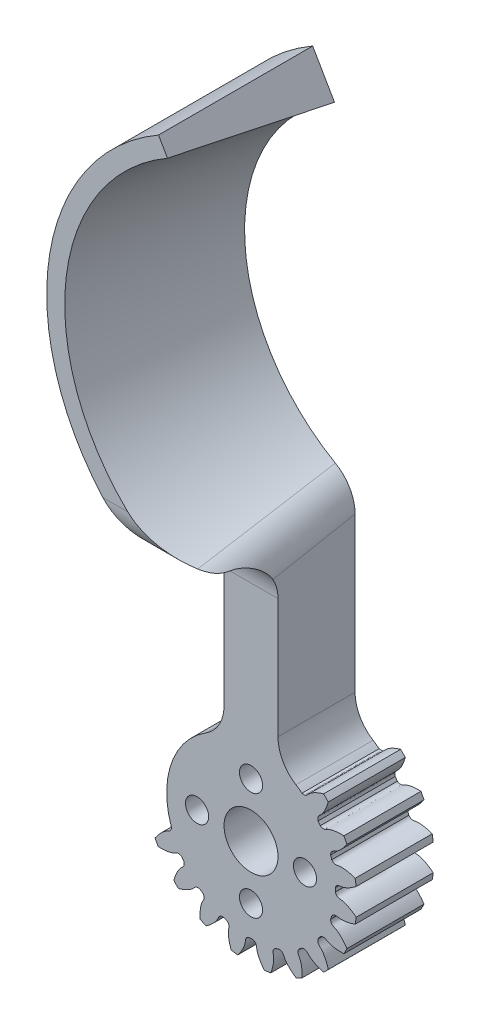
SolidWorks part; units mm, degrees
material "聚脂树脂"
ref_plane "前视基准面" through (0, 0, 0) normal (0, 0, 1) x (1, 0, 0)
ref_plane "上视基准面" through (0, 0, 0) normal (0, 1, 0) x (1, 0, 0)
ref_plane "右视基准面" through (0, 0, 0) normal (1, 0, 0) x (0, 0, -1)
other "Configuration Table"
sketch "草图1" plane through (0, 0, 0) normal (0, 0, 1) x (1, 0, 0)
  circle A0 centre (0, 0) radius 13.75
extrude "凸台-拉伸1" add sketch "草图1" along normal blind 10
ref_axis "基准轴1" through (0, 0, -1.5) along (0, 0, 1)
sketch "草图2" plane through (0, 0, 0) normal (0, 0, 1) x (1, 0, 0)
  line L0 (0, 0) -> (0, 13.75) construction
  circle A0 centre (0, 0) radius 13.75 construction
  arc A1 (0.2416, 10.9348) -> (-0.2416, 10.9348) centre (0, 0) ccw
  arc A2 (3.9764, 15.6228) -> (-3.9764, 15.6228) centre (0, 0) ccw
  spline S0 degree 3 poles (0.2416, 10.9348) (0.764, 11.1168) (0.6964, 11.4839) (0.7661, 11.8375) (0.7736, 11.8719) (0.7829, 11.9108) (0.7941, 11.954) (0.8075, 12.0015) (0.8231, 12.0532) (0.8413, 12.1091) (0.8621, 12.169) (0.8857, 12.2329) (0.9123, 12.3007) (0.9421, 12.3723) (0.9752, 12.4476) (1.0117, 12.5264) (1.0519, 12.6088) (1.0959, 12.6945) (1.1438, 12.7834) (1.1957, 12.8755) (1.2519, 12.9705) (1.3125, 13.0684) (1.3775, 13.1691) (1.4472, 13.2723) (1.5216, 13.3779) (1.601, 13.4858) (1.6853, 13.5958) (1.7747, 13.7078) (1.8694, 13.8216) (1.9693, 13.937) (2.0748, 14.0539) (2.1857, 14.1721) (2.3023, 14.2914) (2.4246, 14.4116) (2.5527, 14.5326) (2.6866, 14.6542) (2.8265, 14.7761) (2.9725, 14.8983) (3.1245, 15.0204) (3.2826, 15.1424) (3.4469, 15.2639) (3.6768, 15.427) (3.8549, 15.5454) (3.9764, 15.6228) knots 0 0 0 0 0.165916 0.170906 0.176664 0.183189 0.190482 0.198542 0.207371 0.216967 0.22733 0.238462 0.250361 0.263027 0.276462 0.290664 0.305634 0.321371 0.337876 0.355149 0.37319 0.391998 0.411574 0.431917 0.453028 0.474907 0.497554 0.520968 0.54515 0.570099 0.595817 0.622302 0.649554 0.677575 0.706363 0.735918 0.766242 0.797333 0.829191 0.861818 0.895212 0.929373 1 1 1 1
  spline S1 degree 3 poles (-0.2416, 10.9348) (-0.764, 11.1168) (-0.6964, 11.4839) (-0.7661, 11.8375) (-0.7736, 11.8719) (-0.7829, 11.9108) (-0.7941, 11.954) (-0.8075, 12.0015) (-0.8231, 12.0532) (-0.8413, 12.1091) (-0.8621, 12.169) (-0.8857, 12.2329) (-0.9123, 12.3007) (-0.9421, 12.3723) (-0.9752, 12.4476) (-1.0117, 12.5264) (-1.0519, 12.6088) (-1.0959, 12.6945) (-1.1438, 12.7834) (-1.1957, 12.8755) (-1.2519, 12.9705) (-1.3125, 13.0684) (-1.3775, 13.1691) (-1.4472, 13.2723) (-1.5216, 13.3779) (-1.601, 13.4858) (-1.6853, 13.5958) (-1.7747, 13.7078) (-1.8694, 13.8216) (-1.9693, 13.937) (-2.0748, 14.0539) (-2.1857, 14.1721) (-2.3023, 14.2914) (-2.4246, 14.4116) (-2.5527, 14.5326) (-2.6866, 14.6542) (-2.8265, 14.7761) (-2.9725, 14.8983) (-3.1245, 15.0204) (-3.2826, 15.1424) (-3.4469, 15.2639) (-3.6768, 15.427) (-3.8549, 15.5454) (-3.9764, 15.6228) knots 0 0 0 0 0.165916 0.170906 0.176664 0.183189 0.190482 0.198542 0.207371 0.216967 0.22733 0.238462 0.250361 0.263027 0.276462 0.290664 0.305634 0.321371 0.337876 0.355149 0.37319 0.391998 0.411574 0.431917 0.453028 0.474907 0.497554 0.520968 0.54515 0.570099 0.595817 0.622302 0.649554 0.677575 0.706363 0.735918 0.766242 0.797333 0.829191 0.861818 0.895212 0.929373 1 1 1 1
extrude "切除-拉伸1" cut sketch "草图2" along normal through all
pattern_circular "阵列(圆周)1" count 20 every 18 about axis through (0, 0, -1.5) along (0, 0, 1) of "切除-拉伸1"
sketch "草图6" plane through (0, 0, 0) normal (0, 0, -1) x (-1, 0, 0)
  line L0 (0, 0) -> (0, 65.9124) construction
  line L1 (0, 0) -> (39.45, 0) construction
  line L2 (0, 0) -> (-30.8379, 0) construction
  line L3 (-12.5, 0) -> (-12.5, 56.4778) construction
  line L4 (3.5, 0) -> (3.5, 35.9714)
  line L5 (-3.5, 0) -> (-3.5, 35.9714)
  line L6 (-3.5, 35.9714) -> (-3.5, 73.8085)
  line L7 (-3.5, 73.8085) -> (-12.5, 58.22) construction
  line L8 (-3.5, 73.8085) -> (6.3052, 90.7916) construction
  line L9 (-3.5, 73.8085) -> (1.2022, 81.9529)
  line L10 (-3.5, 0) -> (3.5, 0)
  line L11 (-5.8534, 12.4419) -> (-3.5, 13.8006)
  line L12 (5.8534, 12.4419) -> (3.5, 13.8006)
  line L13 (2, 83.3347) -> (1.2022, 81.9529)
  circle A0 centre (0, 0) radius 12.5 construction
  circle A1 centre (-12.5, 58.22) radius 24 construction
  circle A2 centre (-12.5, 58.22) radius 27.4044 construction
  arc A3 (1.2022, 81.9529) -> (3.5, 35.9714) centre (-12.5, 58.22) cw
  arc A4 (-0.5, 79.0046) -> (-3.5, 35.9714) centre (-12.5, 58.22) cw
  circle A5 centre (-12.5, 58.22) radius 29 construction
  arc A6 (2, 83.3347) -> (3.5, 34.0332) centre (-12.5, 58.22) cw
  spline S0 degree 3 poles (1668.4324, 1107.449) (-22.4355, -9.6532) (-2.0511, 6.8358) (-4.3931, 11.033) (-4.4189, 11.076) (-4.4589, 11.1387) (-4.5098, 11.2131) (-4.5827, 11.3111) (-4.6712, 11.4208) (-4.7765, 11.541) (-4.8994, 11.6706) (-5.0408, 11.8083) (-5.2016, 11.9528) (-5.3825, 12.1027) (-5.5474, 12.2287) (-5.6899, 12.331) (-25.6073, 26.0378) (-114.7142, -63.0586) (1854.1098, 747.2788) knots -2.172632 -2.172632 -2.172632 -2.172632 0.165916 0.170906 0.183189 0.190482 0.207371 0.22733 0.250361 0.276462 0.305634 0.337876 0.37319 0.411574 0.453028 0.474907 0.497554 12.30377 12.30377 12.30377 12.30377 only from (-3.6089, 10.325) to (-5.8534, 12.4419) construction
  spline S1 degree 3 poles (-3.5, 10.3269) (-4.1564, 10.2919) (-4.2008, 10.6883) (-4.3931, 11.033) (-4.4189, 11.076) (-4.4589, 11.1387) (-4.5098, 11.2131) (-4.5827, 11.3111) (-4.6712, 11.4208) (-4.7765, 11.541) (-4.8994, 11.6706) (-5.0408, 11.8083) (-5.2016, 11.9528) (-5.3825, 12.1027) (-5.5842, 12.2567) (-5.7442, 12.3691) (-5.8366, 12.4308) (-5.8534, 12.4419) knots -0.010289 -0.010289 -0.010289 -0.010289 0.165916 0.170906 0.183189 0.190482 0.207371 0.22733 0.250361 0.276462 0.305634 0.337876 0.37319 0.411574 0.453028 0.497554 0.507432 0.507432 0.507432 0.507432
  spline S2 degree 3 poles (-1668.4324, 1107.449) (22.4355, -9.6532) (2.0511, 6.8358) (4.3931, 11.033) (4.4189, 11.076) (4.4589, 11.1387) (4.5098, 11.2131) (4.5827, 11.3111) (4.6712, 11.4208) (4.7765, 11.541) (4.8994, 11.6706) (5.0408, 11.8083) (5.2016, 11.9528) (5.3825, 12.1027) (5.5474, 12.2287) (5.6899, 12.331) (25.6073, 26.0378) (114.7142, -63.0586) (-1854.1098, 747.2788) knots -1.680063 -1.680063 -1.680063 -1.680063 0.658484 0.663474 0.675757 0.68305 0.699939 0.719899 0.742929 0.76903 0.798202 0.830445 0.865758 0.904142 0.945597 0.967475 0.990122 12.796339 12.796339 12.796339 12.796339 only from (3.6089, 10.325) to (5.8534, 12.4419) construction
  spline S3 degree 3 poles (3.5, 10.3269) (4.1564, 10.2919) (4.2008, 10.6883) (4.3931, 11.033) (4.4189, 11.076) (4.4589, 11.1387) (4.5098, 11.2131) (4.5827, 11.3111) (4.6712, 11.4208) (4.7765, 11.541) (4.8994, 11.6706) (5.0408, 11.8083) (5.2016, 11.9528) (5.3825, 12.1027) (5.5842, 12.2567) (5.7442, 12.3691) (5.8366, 12.4308) (5.8534, 12.4419) knots 0.482279 0.482279 0.482279 0.482279 0.658484 0.663474 0.675757 0.68305 0.699939 0.719899 0.742929 0.76903 0.798202 0.830445 0.865758 0.904142 0.945597 0.990122 1 1 1 1
  dimension "D1" = 25
  dimension "D4" = 48
  dimension "D5" = 30
  dimension "D8" = 58
  dimension "D2" = 7
  dimension "D3" = 58.22
  dimension "D6" = 60
  dimension "D7" = 60
extrude "凸台-拉伸2" add sketch "草图6" against normal blind 20 contours A3 L9 L6 L5 L10 L4 | S1 L5 L11 | L4 S3 L12 | A4 L9 L6 | A6 L13 A3 L4 region at (0, 0.8399, 0) region at (-4.2531, 12.1172, 0) region at (4.2531, 12.1172, 0) region at (-4.0162, 35.0023, 0) region at (-2.8079, 57.8014, 0)
sketch "草图7" plane through (3.5, 0, 0) normal (1, 0, 0) x (0, 0, -1)
  line L2 (-20, 13.8006) -> (-20, 73.8085) construction
  line L7 (-5, 2.5777) -> (-5, 27.3083) construction
  line L8 (-10, 2.5777) -> (0, 2.5777) construction
  line L9 (-20, 34) -> (-20, 0)
  line L10 (-10, 34) -> (-20, 34)
  line L11 (-10, 0) -> (-10, 34)
  line L12 (-20, 0) -> (-10, 0)
  line L13 (-10, 10.3269) -> (-10, 0) construction
  line L14 (-20, 0) -> (-10, 0) construction
  dimension "D1" = 34
extrude "切除-拉伸3" cut sketch "草图7" against normal blind 32 and the other way blind 10
ref_plane "基准面1" through (12.5, 0, 0) normal (1, 0, 0) x (0, 0, -1)
sketch "草图4" plane through (0, 0, 10) normal (0, 0, 1) x (1, 0, 0)
  line L0 (0, 0) -> (0, 14.4175) construction
  line L1 (0, 0) -> (19.7904, 0) construction
  circle A0 centre (0, 0) radius 9
  circle A1 centre (0, 0) radius 3.5
  circle A2 centre (0, 7) radius 1.5
  circle A3 centre (7, 0) radius 1.5
  circle A4 centre (0, -7) radius 1.5
  circle A5 centre (-7, 0) radius 1.5
  dimension "D1" = 18
  dimension "D2" = 7
  dimension "D3" = 3
  dimension "D4" = 3
  dimension "D5" = 7
  dimension "D6" = 7
extrude "切除-拉伸2" cut sketch "草图4" against normal blind 20 contours A1 | A5 | A2 | A3 | A4
ref_plane "基准面2" through (0, 0, 9) normal (0, 0, 1) x (1, 0, 0)
sketch "草图17" plane through (0, 0, 10) normal (0, 0, 1) x (1, 0, 0)
  line L0 (0, 0) -> (-6.6228, 8.7044)
  line L1 (-6.6228, 8.7044) -> (-11.857, 15.5837)
  line L2 (0, 0) -> (-10.325, -3.6089)
  line L3 (-10.325, -3.6089) -> (-17.9409, -6.2709)
  circle A0 centre (0, 0) radius 10.9375
  arc A1 (-6.2318, 8.9885) -> (-6.6228, 8.7044) centre (0, 0) ccw construction
  circle A2 centre (0, 0) radius 17.5
  dimension "D1" = 35
extrude "切除-拉伸5" cut sketch "草图17" against normal blind 10 contours L1 A2 L3 A0 region at (-12.9643, 3.8979, 10)
sketch "草图20" plane through (0, 0, 0) normal (0, 0, -1) x (-1, 0, 0)
  line L0 (-3.5, 13.8006) -> (-3.5, 10.3624)
  line L1 (3.5, 13.8006) -> (3.5, 10.3624)
  line L2 (5.8534, 12.4419) -> (3.5, 13.8006) construction
  line L3 (-5.8534, 12.4419) -> (-3.5, 13.8006) construction
  line L4 (5.8534, 12.4419) -> (3.5, 13.8006)
  line L5 (-5.8534, 12.4419) -> (-3.5, 13.8006)
  circle A0 centre (0, 0) radius 10.9375
  arc A1 (10.325, -3.6089) -> (6.2318, 8.9885) centre (0, 0) ccw construction
  arc A2 (6.6252, 12.0486) -> (5.8534, 12.4419) centre (0, 0) ccw construction
  arc A3 (-5.8534, 12.4419) -> (-6.6252, 12.0486) centre (0, 0) ccw construction
  arc A4 (6.6252, 12.0486) -> (5.8534, 12.4419) centre (0, 0) ccw
  arc A5 (-5.8534, 12.4419) -> (-6.6252, 12.0486) centre (0, 0) ccw
  spline S0 degree 3 poles (1876.625, -698.848) (-20.9969, 12.4766) (4.3246, 5.6774) (6.3437, 10.0391) (6.3633, 10.0853) (6.3905, 10.1545) (6.4208, 10.2394) (6.4573, 10.356) (6.4939, 10.4921) (6.5293, 10.6479) (6.5619, 10.8235) (6.5902, 11.0188) (6.6126, 11.2338) (6.6276, 11.4683) (6.6325, 11.6758) (6.6315, 11.8512) (6.0134, 36.0214) (-118.4428, 55.7409) (1694.3797, -1060.7669) knots -2.172632 -2.172632 -2.172632 -2.172632 0.165916 0.170906 0.183189 0.190482 0.207371 0.22733 0.250361 0.276462 0.305634 0.337876 0.37319 0.411574 0.453028 0.474907 0.497554 12.30377 12.30377 12.30377 12.30377 only from (6.2318, 8.9885) to (6.6252, 12.0486) construction
  spline S1 degree 3 poles (-1876.625, -698.848) (20.9969, 12.4766) (-4.3246, 5.6774) (-6.3437, 10.0391) (-6.3633, 10.0853) (-6.3905, 10.1545) (-6.4208, 10.2394) (-6.4573, 10.356) (-6.4939, 10.4921) (-6.5293, 10.6479) (-6.5619, 10.8235) (-6.5902, 11.0188) (-6.6126, 11.2338) (-6.6276, 11.4683) (-6.6325, 11.6758) (-6.6315, 11.8512) (-6.0134, 36.0214) (118.4428, 55.7409) (-1694.3797, -1060.7669) knots -1.680063 -1.680063 -1.680063 -1.680063 0.658484 0.663474 0.675757 0.68305 0.699939 0.719899 0.742929 0.76903 0.798202 0.830445 0.865758 0.904142 0.945597 0.967475 0.990122 12.796339 12.796339 12.796339 12.796339 only from (-6.2318, 8.9885) to (-6.6252, 12.0486) construction
  spline S2 degree 3 poles (6.2318, 8.9885) (5.9162, 9.4428) (6.1867, 9.7) (6.3437, 10.0391) (6.3633, 10.0853) (6.3905, 10.1545) (6.4208, 10.2394) (6.4573, 10.356) (6.4939, 10.4921) (6.5293, 10.6479) (6.5619, 10.8235) (6.5902, 11.0188) (6.6126, 11.2338) (6.6276, 11.4683) (6.6336, 11.722) (6.6305, 11.9176) (6.6261, 12.0285) (6.6252, 12.0486) knots 0 0 0 0 0.165916 0.170906 0.183189 0.190482 0.207371 0.22733 0.250361 0.276462 0.305634 0.337876 0.37319 0.411574 0.453028 0.497554 0.507432 0.507432 0.507432 0.507432
  spline S3 degree 3 poles (-6.2318, 8.9885) (-5.9162, 9.4428) (-6.1867, 9.7) (-6.3437, 10.0391) (-6.3633, 10.0853) (-6.3905, 10.1545) (-6.4208, 10.2394) (-6.4573, 10.356) (-6.4939, 10.4921) (-6.5293, 10.6479) (-6.5619, 10.8235) (-6.5902, 11.0188) (-6.6126, 11.2338) (-6.6276, 11.4683) (-6.6336, 11.722) (-6.6305, 11.9176) (-6.6261, 12.0285) (-6.6252, 12.0486) knots 0.492568 0.492568 0.492568 0.492568 0.658484 0.663474 0.675757 0.68305 0.699939 0.719899 0.742929 0.76903 0.798202 0.830445 0.865758 0.904142 0.945597 0.990122 1 1 1 1
extrude "切除-拉伸7" cut sketch "草图20" against normal blind 10 contours S3 A0 L0 L5 A5 | A0 S2 A4 L4 L1 region at (4.956, 11.3958, 0) region at (-4.956, 11.3958, 0)
fillet "圆角7" radius 5 2 edges at (-3.5, 10.3624, 5) (3.5, 10.3624, 5)
ref_plane "基准面4" through (0, 58.22, 0) normal (0, 1, 0) x (1, 0, 0)
ref_axis "基准轴3" through (12.5, 58.22, -6) along (0, 0, 1)
sketch "草图21" plane through (12.5, 0, 0) normal (1, 0, 0) x (0, 0, -1)
  line L0 (0, 0) -> (12.6235, 0) construction
  line L1 (-41.0199, 58.22) -> (51.9091, 58.22) construction
  line L6 (-10, 13.4816) -> (-10, 87.3784) construction
  line L12 (-40, 58.22) -> (-40, 88.22)
  line L13 (-40, 88.22) -> (20, 78.22)
  line L14 (20, 78.22) -> (20, 58.22)
  line L15 (20, 58.22) -> (-40, 58.22)
  line L16 (-20, 83.3347) -> (-20, 87.908) construction
  line L17 (0, 73.8085) -> (0, 87.908) construction
  line L48 (-10, 13.4816) -> (-10, 34) construction
  dimension "D1" = 58.22
  dimension "D2" = 30
  dimension "D3" = 20
  dimension "D4" = 60
  dimension "D5" = 30
revolve "切除-旋转7" cut sketch "草图21" angle 360 about L1 region at (12.5, 70.8867, 12)
fillet "圆角9" radius 3 1 edges at (-3.5, 34.0332, 10)
fillet "圆角11" radius 5 2 edges at (-0.2094, 34, 10) (-1.2884, 34, 20)
fillet "圆角12" radius 5 1 edges
